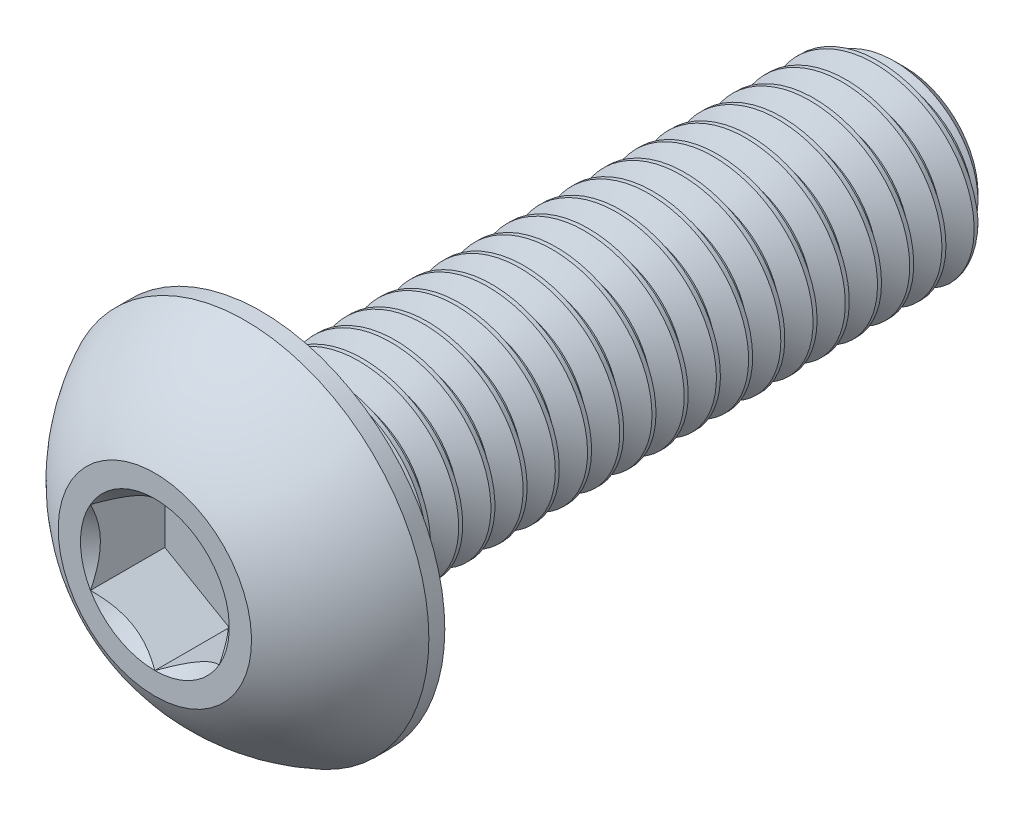
SolidWorks part; units mm, degrees
ref_plane "Front" through (0, 0, 0) normal (0, 0, 1) x (1, 0, 0)
ref_plane "Top" through (0, 0, 0) normal (0, 1, 0) x (1, 0, 0)
ref_plane "Right" through (0, 0, 0) normal (1, 0, 0) x (0, 0, -1)
sketch "Sketch1" plane through (0, 0, 0) normal (1, 0, 0) x (0, 0, -1)
  line L2 (1.65, 1.5) -> (11.65, 1.5)
  line L3 (11.65, 1.5) -> (11.65, 0)
  line L4 (11.65, 0) -> (1.65, 0)
  line L6 (1.4025, 2.85) -> (1.65, 2.85) construction
  line L7 (11.65, 1.5) -> (11.65, -1.5) construction
  line L8 (0, 0) -> (1.65, 0) construction
  line L9 (1.65, 2.85) -> (1.65, -2.85) construction
  line L11 (1.65, 1.5) -> (1.65, 0)
  line L13 (0, 1) -> (0, -1) construction
  line L14 (0, 1) -> (0, 1.5) construction
  arc A3 (0, 1.5) -> (1.4025, 2.85) centre (2.7948, 0) cw construction
  dimension "D1" = 0.2475
  dimension "Head Ht" = 1.65
  dimension "Head Dia" = 5.7
  dimension "Dia" = 3
  dimension "Lg" = 10
  dimension "Hex" = 2
revolve "Revolve1" add sketch "Sketch1" angle 360 mid plane about L4
sketch "Sketch3" plane through (0, 0, -11.65) normal (0, 0, -1) x (-1, 0, 0)
  circle A0 centre (0, 0) radius 1.5
curve "Helix/Spiral1" pitch 0.5 height 10.5 radius 1.5 centre (0, 0, -11.65) axis (0, 0, 1) start towards (0, 1, 0)
sketch "Sketch2" plane through (0, 0, 0) normal (1, 0, 0) x (0, 0, -1)
  line L0 (11.65, 1.5) -> (12.0875, 1.5)
  line L1 (12.0875, 1.5) -> (11.9, 1.1752)
  line L2 (11.9, 1.1752) -> (11.8375, 1.1752)
  line L3 (11.8375, 1.1752) -> (11.65, 1.5)
  line L4 (11.7438, 1.3376) -> (11.9938, 1.3376) construction
  dimension "D1" = 60
  dimension "D2" = 0.0625
  dimension "D3" = 0.25
chamfer "Chamfer1" distance 0.375 angle 45 1 edges at (0, 1.5, -11.65)
sweep "Cut-Sweep1" cut profiles "Sketch2" path "Helix/Spiral1"
sketch "Sketch7" plane through (0, 0, 0) normal (1, 0, 0) x (0, 0, -1)
  line L6 (1.4025, 2.85) -> (1.65, 2.85) construction
  line L8 (0, 0) -> (1.65, 0) construction
  line L11 (1.65, 2.85) -> (1.65, -2.85) construction
  line L12 (1.4025, 2.85) -> (1.65, 2.85)
  line L13 (0, 0) -> (1.65, 0)
  line L14 (0, 1) -> (0, -1) construction
  line L15 (1.65, 2.85) -> (1.65, 0)
  line L16 (0, 1.5) -> (0, 0)
  arc A2 (1.4025, 2.85) -> (0, 1.5) centre (2.7948, 0) ccw construction
  arc A3 (1.4025, 2.85) -> (0, 1.5) centre (2.7948, 0) ccw
revolve "Revolve2" add sketch "Sketch7" angle 360 mid plane about L13
sketch "Sketch5" plane through (0, 0, 0) normal (0, 0, 1) x (1, 0, 0)
  line L1 (1, -0.5774) -> (1, 0.5774)
  line L2 (1, 0.5774) -> (0, 1.1547)
  line L3 (0, 1.1547) -> (-1, 0.5774)
  line L4 (-1, 0.5774) -> (-1, -0.5774)
  line L5 (-1, -0.5774) -> (0, -1.1547)
  line L6 (0, -1.1547) -> (1, -0.5774)
  circle A0 centre (0, 0) radius 1 construction
extrude "Cut-Extrude2" cut sketch "Sketch5" against normal blind 1.155
sketch "Sketch6" plane through (0, 0, 0) normal (0, 0, 1) x (1, 0, 0)
  circle A0 centre (0, 0) radius 1.1547
extrude "Cut-Extrude3" cut sketch "Sketch6" against normal blind 1.155 draft 45
sketch "Sketch9" [suppressed] plane through (0, 0, -4.2164) normal (0, 0, 1) x (1, 0, 0)
  circle A2 centre (0, 0) radius 3.9687
extrude "Boss-Extrude2" [suppressed] add sketch "Sketch9" against normal offset from surface (9.525 mm away) 28.575 up to face at (0, 1.125, -11.65)
sketch "Sketch10" plane through (0, 0, 0) normal (1, 0, 0) x (0, 0, -1)
  line L0 (11.65, 1.5) -> (11.65, -1.5) construction
  point P0 (10.9, -1.5)
  dimension "D1" = 0.75
equation "\"D3@Helix/Spiral1\" = \"Lg@Sketch1\" + \"D4@Helix/Spiral1\""
equation "\"D2@Sketch2\" = \"D4@Helix/Spiral1\" * .125"
equation "\"D3@Sketch2\" = \"D4@Helix/Spiral1\" * .5"
equation "\"D1@Chamfer1\" = \"D4@Helix/Spiral1\" * .75"
equation "\"D1@Cut-Extrude2\" = \"Head Ht@Sketch1\" * .7"
equation "\"D1@Sketch1\" = \"Head Ht@Sketch1\" * .15"
equation "\"D1@Sketch10\" = \"D4@Helix/Spiral1\" * 1.5"
equation "\"D1@Cut-Extrude3\" = \"D1@Cut-Extrude2\""
